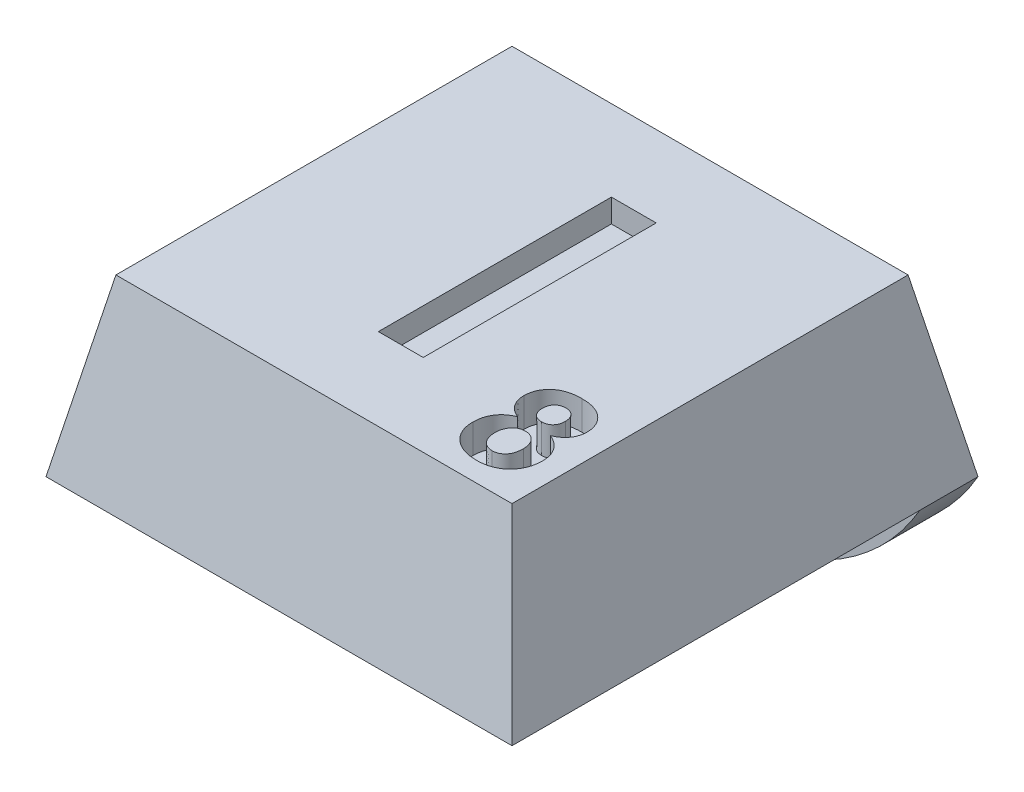
SolidWorks part; units mm, degrees
ref_plane "Front Plane" through (0, 0, 0) normal (0, 0, 1) x (1, 0, 0)
ref_plane "Top Plane" through (0, 0, 0) normal (0, 1, 0) x (1, 0, 0)
ref_plane "Right Plane" through (0, 0, 0) normal (1, 0, 0) x (0, 0, -1)
sketch "Sketch1" plane through (0, 0, 0) normal (0, 1, 0) x (1, 0, 0)
  line L1 (0, 0) -> (8, 0)
  line L2 (0, 0) -> (0, 8)
  line L3 (0, 8) -> (8, 8)
  line L4 (8, 0) -> (8, 8)
  dimension "D1" = 8
  dimension "D2" = 8
extrude "Boss-Extrude1" add sketch "Sketch1" along normal blind 3
sketch "Sketch2" plane through (0, 0, 0) normal (0, 0, 1) x (1, 0, 0)
  line L0 (0, 0) -> (0.6, 3)
  line L1 (0, 3) -> (8, 3) construction
  line L2 (0.6, 3) -> (0, 3)
  line L3 (0, 3) -> (0, 0)
  line L4 (8, 0) -> (7.4, 3)
  line L5 (7.4, 3) -> (8, 3)
  line L6 (8, 3) -> (8, 0)
  dimension "D1" = 0.6
  dimension "D2" = 0.6
extrude "Cut-Extrude1" cut sketch "Sketch2" against normal through all both and the other way through all
sketch "Sketch3" plane through (0, 0, 0) normal (1, 0, 0) x (0, 0, -1)
  line L0 (0, 0) -> (0.6, 3)
  line L1 (8, 3) -> (0, 3) construction
  line L2 (0.6, 3) -> (0, 3)
  line L3 (0, 3) -> (0, 0)
  line L4 (8, 3) -> (7.4, 3)
  line L5 (7.4, 3) -> (8, 0)
  line L6 (8, 3) -> (8, 0)
  dimension "D1" = 0.6
  dimension "D2" = 0.6
extrude "Cut-Extrude2" cut sketch "Sketch3" along normal blind 11
sketch "Sketch4" plane through (0, 0, 0) normal (0, -1, 0) x (1, 0, 0)
  line L0 (8, 0) -> (8, -8) construction
  line L3 (0, 0) -> (8, 0) construction
  circle A0 centre (4, -3.75) radius 1.75
  dimension "D1" = 3.5
  dimension "D2" = 4
  dimension "D3" = 3.75
extrude "Cut-Extrude3" cut sketch "Sketch4" against normal blind 0.4
sketch "Sketch5" plane through (0, 0, 0) normal (0, -1, 0) x (1, 0, 0)
  line L0 (8, 0) -> (8, -8) construction
  line L1 (0, -8) -> (8, -8)
  line L2 (0, -8) -> (0, -7)
  line L3 (0, -7) -> (8, -7)
  line L4 (8, -8) -> (8, -7)
  dimension "D1" = 1
extrude "Boss-Extrude2" add sketch "Sketch5" along normal blind 2
fillet "Fillet1" radius 4 2 edges at (8, -2, -7.5) (0, -2, -7.5)
sketch "Sketch6" plane through (0, 3, 0) normal (0, 1, 0) x (1, 0, 0)
  text T0 "I" font "Arial" height 4
extrude "Cut-Extrude4" cut sketch "Sketch6" against normal blind 0.4
sketch "Sketch7" plane through (0, 3, 0) normal (0, 1, 0) x (1, 0, 0)
  text T0 "8" font "Arial" height 1.8
extrude "Cut-Extrude5" cut sketch "Sketch7" against normal blind 0.5
